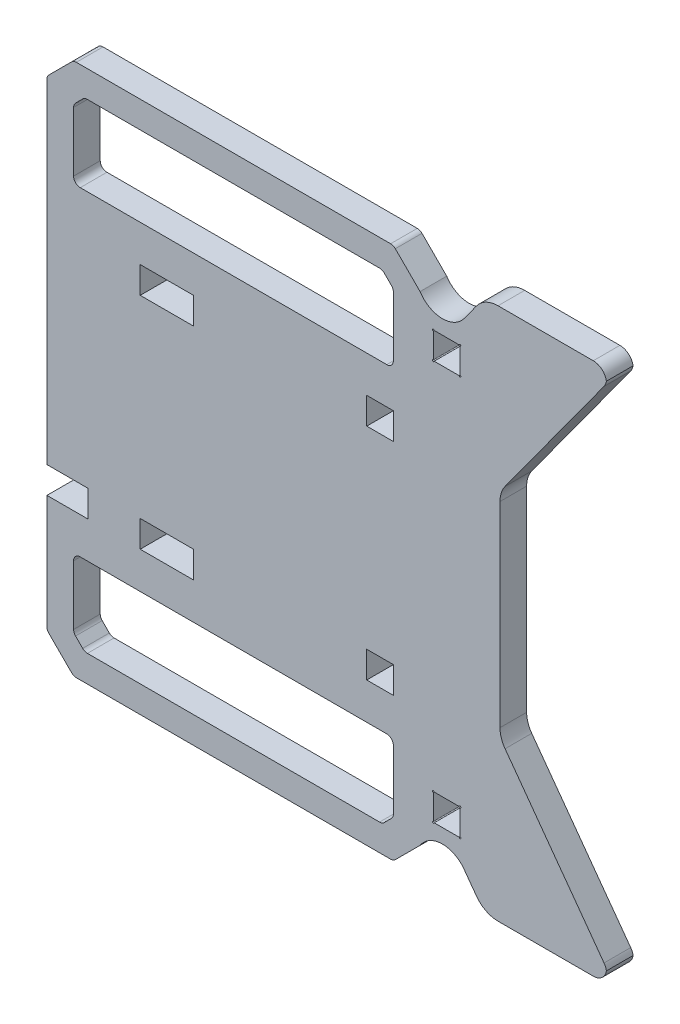
SolidWorks part; units mm, degrees
ref_plane "Front Plane" through (0, 0, 0) normal (0, 0, 1) x (1, 0, 0)
ref_plane "Top Plane" through (0, 0, 0) normal (0, 1, 0) x (1, 0, 0)
ref_plane "Right Plane" through (0, 0, 0) normal (1, 0, 0) x (0, 0, -1)
sketch "Sketch1" plane through (0, 0, 0) normal (0, 0, 1) x (1, 0, 0)
  line L0 (83.672, 0) -> (-43.8164, 0) construction
  line L1 (10.525, 38.1) -> (10.525, -38.1) construction
  line L2 (-27.575, 38.1) -> (48.625, 38.1)
  line L3 (99.425, -63.5) -> (99.425, -60.325)
  line L4 (99.425, -60.325) -> (74.025, -25.4)
  line L5 (-27.575, -63.5) -> (48.625, -63.5)
  line L6 (-27.575, 38.1) -> (-27.575, 54.5197)
  line L7 (48.625, 38.1) -> (48.625, 54.5197)
  line L8 (-24.9447, 57.15) -> (45.9947, 57.15)
  line L9 (-27.575, 63.5) -> (48.625, 63.5)
  line L10 (-33.925, 57.15) -> (-33.925, -57.15)
  line L11 (-27.575, 63.5) -> (-33.925, 57.15)
  line L12 (-24.9447, 57.15) -> (-27.575, 54.5197)
  line L13 (99.425, 63.5) -> (99.425, 60.325)
  line L14 (-23.0849, 59.0099) -> (-29.4349, 52.6599) construction
  line L15 (99.425, 60.325) -> (74.025, 25.4)
  line L16 (74.025, 25.4) -> (74.025, -25.4)
  line L17 (48.625, -38.1) -> (48.625, -54.5197)
  line L18 (-27.575, -38.1) -> (48.625, -38.1)
  line L19 (-24.9447, -57.15) -> (45.9947, -57.15)
  line L20 (-24.9447, -57.15) -> (-27.575, -54.5197)
  line L21 (-27.575, -38.1) -> (-27.575, -54.5197)
  line L22 (-27.575, -63.5) -> (-33.925, -57.15)
  line L23 (48.625, -63.5) -> (54.975, -57.15)
  line L24 (48.625, 63.5) -> (54.975, 57.15)
  line L25 (70.3271, -63.5) -> (99.425, -63.5)
  line L26 (45.9947, 57.15) -> (48.625, 54.5197)
  line L27 (45.9947, -57.15) -> (48.625, -54.5197)
  line L28 (70.3271, 63.5) -> (65.7089, 57.15)
  line L29 (70.3271, 63.5) -> (99.425, 63.5)
  line L30 (78.8831, 75.2646) -> (53.4831, 40.3396) construction
  line L31 (54.975, -42.3909) -> (54.975, -57.15)
  line L32 (70.3271, -63.5) -> (65.7089, -57.15)
  line L34 (48.625, -63.5) -> (54.975, -57.15)
  line L35 (65.7089, 57.15) -> (54.975, 42.3909)
  line L36 (54.975, 42.3909) -> (54.975, 57.15)
  line L37 (65.7089, -57.15) -> (54.975, -42.3909)
  point P7 (-27.575, 0)
  point P21 (74.025, 0)
  point P22 (-33.925, 0)
  dimension "D1" = 25.4
  dimension "D2" = 76.2
  dimension "D3" = 127
  dimension "D4" = 6.35
  dimension "D7" = 3.175
  dimension "D8" = 25.4
  dimension "D9" = 25.4
  dimension "D6" = 6.35
extrude "Boss-Extrude1" add sketch "Sketch1" along normal blind 6.35 contours L23 L32 L25 L3 L4 L16 L15 L13 L29 L28 L24 L9 L11 L10 L22 L5 L8 L26 L7 L2 L6 L12 L27 L19 L20 L21 L18 L17 region at (27.1557, 0, 0)
fillet "Fillet1" radius 6.35 4 edges at (70.3271, 63.5, 3.175) (70.3271, -63.5, 3.175) (54.975, -42.3909, 3.175) (54.975, 42.3909, 3.175)
fillet "Fillet3" radius 3.175 4 edges at (99.425, 63.5, 3.175) (99.425, 60.325, 3.175) (99.425, -60.325, 3.175) (99.425, -63.5, 3.175)
fillet "Fillet4" radius 6.35 2 edges at (74.025, -25.4, 3.175) (74.025, 25.4, 3.175)
fillet "Fillet7" radius 1.5875 4 edges at (-27.575, -38.1, 3.175) (48.625, -38.1, 3.175) (48.625, 38.1, 3.175) (-27.575, 38.1, 3.175)
fillet "Fillet8" radius 1.5875 6 edges at (-33.925, -57.15, 3.175) (-27.575, -63.5, 3.175) (48.625, -63.5, 3.175) (48.625, 63.5, 3.175) (-27.575, 63.5, 3.175) (-33.925, 57.15, 3.175)
fillet "Fillet9" radius 1.5875 8 edges at (-27.575, 54.5197, 3.175) (-24.9447, 57.15, 3.175) (-27.575, -54.5197, 3.175) (-24.9447, -57.15, 3.175) (45.9947, -57.15, 3.175) (48.625, -54.5197, 3.175) (48.625, 54.5197, 3.175) (45.9947, 57.15, 3.175)
sketch "Sketch2" plane through (0, 0, 6.35) normal (0, 0, 1) x (1, 0, 0)
  line L0 (-33.925, 0) -> (74.025, 0) construction
  line L1 (-33.925, 56.4924) -> (-33.925, -56.4924) construction
  line L2 (74.025, 23.3351) -> (74.025, -23.3351) construction
  line L3 (48.625, 39.6875) -> (48.625, 53.8622) construction
  line L4 (58.3484, 50.8) -> (64.3016, 50.8)
  line L5 (58.15, 50.6016) -> (58.15, 44.6484)
  line L6 (58.3484, 44.45) -> (64.3016, 44.45)
  line L7 (64.5, 50.6016) -> (64.5, 44.6484)
  line L8 (64.5, -50.6016) -> (64.5, -44.6484)
  line L9 (58.3484, -50.8) -> (64.3016, -50.8)
  line L10 (58.15, -50.6016) -> (58.15, -44.6484)
  line L11 (58.3484, -44.45) -> (64.3016, -44.45)
  arc A0 (58.3484, 50.8) -> (58.15, 50.6016) centre (58.15, 50.8) ccw
  arc A1 (64.5, 50.6016) -> (64.3016, 50.8) centre (64.5, 50.8) ccw
  arc A2 (64.3016, 44.45) -> (64.5, 44.6484) centre (64.5, 44.45) ccw
  arc A3 (58.15, 44.6484) -> (58.3484, 44.45) centre (58.15, 44.45) ccw
  arc A4 (64.3016, -44.45) -> (64.5, -44.6484) centre (64.5, -44.45) cw
  arc A5 (64.5, -50.6016) -> (64.3016, -50.8) centre (64.5, -50.8) cw
  arc A6 (58.3484, -50.8) -> (58.15, -50.6016) centre (58.15, -50.8) cw
  arc A7 (58.15, -44.6484) -> (58.3484, -44.45) centre (58.15, -44.45) cw
  point P10 (48.625, 46.7748)
  dimension "D5" = 0.3969
  dimension "D6" = 0.3969
  dimension "D7" = 0.3969
  dimension "D8" = 0.3969
  dimension "D1" = 6.35
  dimension "D2" = 6.35
  dimension "D3" = 50.8
  dimension "D4" = 9.525
extrude "Cut-Extrude1" cut sketch "Sketch2" against normal through all
sketch "Sketch3" plane through (0, 0, 6.35) normal (0, 0, 1) x (1, 0, 0)
  line L0 (1, 29.3687) -> (1, -29.3687) construction
  line L1 (44.8469, 29.3687) -> (44.8469, -29.3687) construction
  line L2 (48.4188, 29.3687) -> (41.275, 29.3687) construction
  line L3 (48.4187, -29.3687) -> (41.275, -29.3687) construction
  line L4 (44.8469, 0) -> (-40.6002, 0) construction
  line L5 (1, 29.3687) -> (-11.7, 29.3687)
  line L6 (1, -29.3687) -> (-11.7, -29.3687)
  line L7 (1, -29.3687) -> (1, -23.0187)
  line L8 (1, -23.0187) -> (-11.7, -23.0187)
  line L9 (-11.7, -29.3687) -> (-11.7, -23.0187)
  line L10 (42.275, -29.3687) -> (48.625, -29.3687)
  line L11 (42.275, -29.3687) -> (42.275, -23.0187)
  line L12 (42.275, -23.0187) -> (48.625, -23.0187)
  line L13 (48.625, -29.3687) -> (48.625, -23.0187)
  line L14 (1, 29.3687) -> (1, 23.0187)
  line L15 (-11.7, 29.3687) -> (-11.7, 23.0187)
  line L16 (1, 23.0187) -> (-11.7, 23.0187)
  line L17 (48.625, 29.3687) -> (48.625, 23.0187)
  line L18 (42.275, 29.3687) -> (48.625, 29.3687)
  line L19 (42.275, 29.3687) -> (42.275, 23.0187)
  line L20 (42.275, 23.0187) -> (48.625, 23.0187)
  line L21 (-33.925, 56.4924) -> (-33.925, -56.4924) construction
  line L22 (-33.925, -29.3687) -> (-24.1, -29.3687)
  line L23 (-33.925, -29.3687) -> (-33.925, -23.0187)
  line L24 (-33.925, -23.0187) -> (-24.1, -23.0187)
  line L25 (-24.1, -29.3687) -> (-24.1, -23.0187)
  line L26 (-24.1, -29.3687) -> (-33.925, -29.3687) construction
  dimension "D1" = 6.35
  dimension "D2" = 12.7
  dimension "D3" = 6.35
  dimension "D4" = 6.35
extrude "Cut-Extrude2" cut sketch "Sketch3" against normal through all
